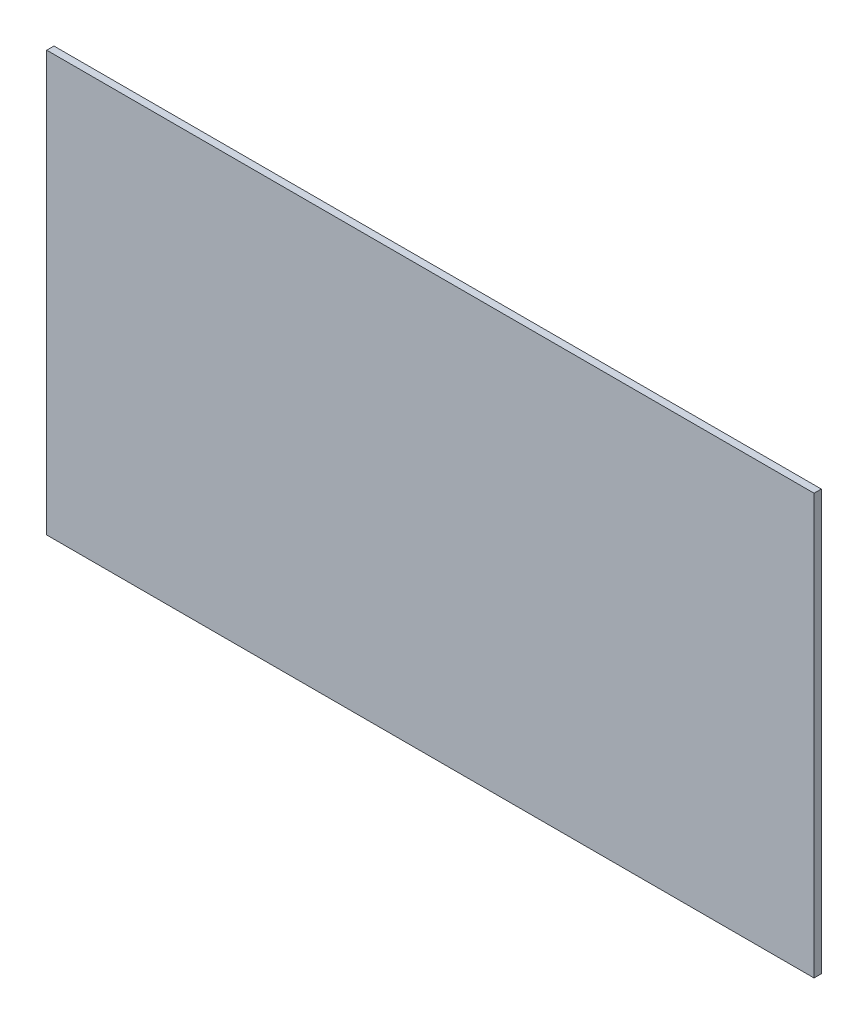
SolidWorks part; units mm, degrees
material "POM Acetal Copolymer"
ref_plane "Front Plane" through (0, 0, 0) normal (0, 0, 1) x (1, 0, 0)
ref_plane "Top Plane" through (0, 0, 0) normal (0, 1, 0) x (1, 0, 0)
ref_plane "Right Plane" through (0, 0, 0) normal (1, 0, 0) x (0, 0, -1)
sketch "Sketch1" plane through (0, 0, 0) normal (0, 0, 1) x (1, 0, 0)
  line L8 (65.0697, 118.2639) -> (65.0697, 110.8979)
  line L9 (65.0697, 110.8979) -> (78.5317, 110.8979)
  line L10 (78.5317, 110.8979) -> (78.5317, 118.2639)
  line L11 (78.5317, 118.2639) -> (65.0697, 118.2639)
extrude "Boss-Extrude1" add sketch "Sketch1" along normal blind 0.127
sketch "Legend Ref" plane through (0, 0, 0) normal (0, 0, -1) x (-1, 0, 0)
  line L1 (-78.5317, 110.8979) -> (-78.5317, 118.2639) construction
  line L2 (-65.0697, 118.2639) -> (-65.0697, 110.8979) construction
  line L3 (-78.5317, 112.8664) -> (-65.0697, 112.8664) construction
  line L4 (-78.5317, 114.5809) -> (-65.0697, 114.5809) construction
  point P8 (-65.0697, 114.5809)
  dimension "D1" = 1.7145
sketch "LONG TEXT Sketch" plane through (0, 0, 0) normal (0, 0, -1) x (-1, 0, 0)
  text T0 "------" font "GordonURWCon" height in points 13
wrap "LONG TEXT" [suppressed] sketch "LONG TEXT Sketch" source sketch "LONG TEXT Sketch" thickness 0.0254 parameters "D1"=0.0254
sketch "Sketch3" plane through (0, 0, 0) normal (0, 0, -1) x (-1, 0, 0)
  line L0 (-76.8807, 114.5809) -> (-66.7207, 114.5809) construction
  line L2 (-71.8007, 110.8979) -> (-71.8007, 118.2639) construction
  line L4 (-78.5317, 118.2639) -> (-65.0697, 118.2639) construction
  line L5 (-76.8807, 114.1999) -> (-66.7207, 114.1999)
  line L6 (-76.8807, 114.9619) -> (-66.7207, 114.9619)
  line L7 (-76.8807, 114.1999) -> (-76.8807, 114.9619)
  line L8 (-66.7207, 114.1999) -> (-66.7207, 114.9619)
  line L9 (-65.0697, 110.8979) -> (-78.5317, 110.8979) construction
  point P12 (-71.8007, 114.5809)
  dimension "D1" = 10.16
  dimension "D2" = 0.381
  dimension "D3" = 0.381
wrap "BLANK Legend" sketch "Sketch3" wrap type scribe source sketch "Sketch3" face at (71.8007, 114.5809, 0)
sketch "SHORT TEXT Sketch" plane through (0, 0, 0) normal (0, 0, -1) x (-1, 0, 0)
  text T0 "------" font "GordonURWMed" height in points 14
wrap "SHORT TEXT" [suppressed] sketch "SHORT TEXT Sketch" source sketch "SHORT TEXT Sketch"
equation "\"D2@Sketch3\"=\"D3@Sketch3\""
